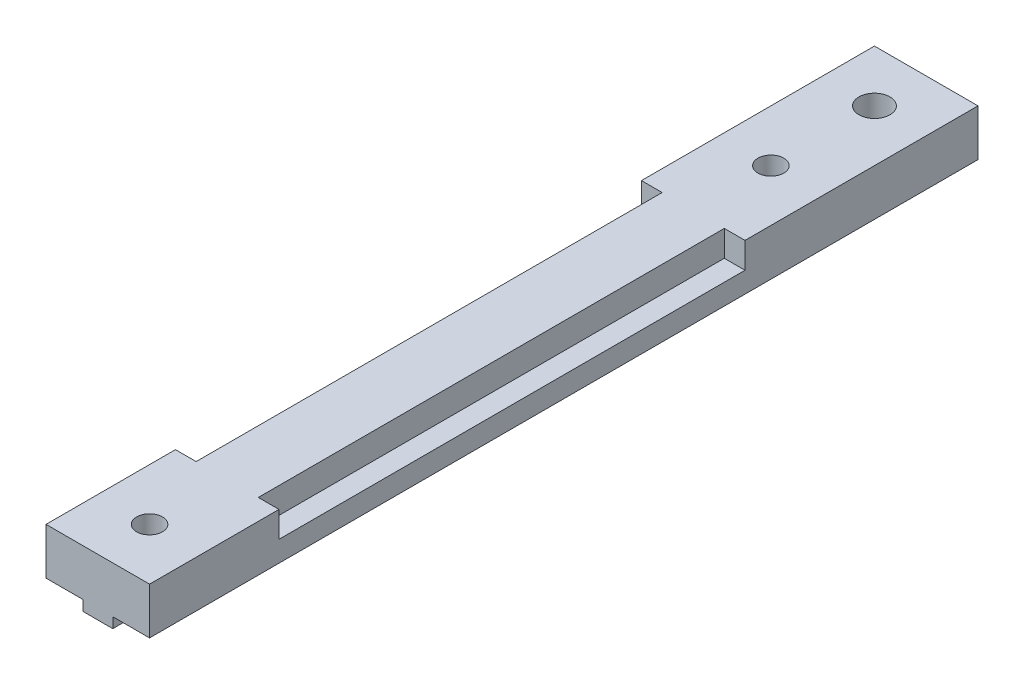
SolidWorks part; units mm, degrees
ref_plane "Front Plane" through (0, 0, 0) normal (0, 0, 1) x (1, 0, 0)
ref_plane "Top Plane" through (0, 0, 0) normal (0, 1, 0) x (1, 0, 0)
ref_plane "Right Plane" through (0, 0, 0) normal (1, 0, 0) x (0, 0, -1)
sketch "Sketch1" plane through (0, 0, 0) normal (0, 0, 1) x (1, 0, 0)
  line L0 (-5, 0) -> (5, 0)
  line L1 (5, 0) -> (5, -4.5)
  line L2 (5, -4.5) -> (1.45, -4.5)
  line L3 (1.45, -4.5) -> (1.45, -5.5)
  line L4 (1.45, -5.5) -> (-1.45, -5.5)
  line L5 (-1.45, -5.5) -> (-1.45, -4.5)
  line L6 (-1.45, -4.5) -> (-5, -4.5)
  line L7 (-5, -4.5) -> (-5, 0)
  point P6 (0, 0)
  point P9 (0, 0)
  dimension "D1" = 10
  dimension "D2" = 4.5
  dimension "D3" = 1
  dimension "D4" = 2.9
extrude "Main" add sketch "Sketch1" along normal blind 80
sketch "Sketch2" plane through (0, 0, 0) normal (0, 1, 0) x (1, 0, 0)
  line L0 (5, -80) -> (-5, -80) construction
  line L1 (5, 0) -> (-5, 0) construction
  circle A0 centre (0, -75) radius 1.25
  circle A1 centre (0, -15) radius 1.25
  circle A2 centre (0, -5) radius 1.5
  point P9 (0, 0)
  dimension "D1" = 2.5
  dimension "D4" = 3
  dimension "D2" = 5
  dimension "D3" = 60
  dimension "D5" = 5
extrude "Cut-Extrude1" cut sketch "Sketch2" against normal through all
sketch "Sketch3" plane through (0, 0, 0) normal (0, 1, 0) x (1, 0, 0)
  line L0 (-5, -80) -> (-5, 0) construction
  line L1 (-5, -22.5) -> (-3, -22.5)
  line L2 (-5, -22.5) -> (-5, -67.5)
  line L3 (-5, -67.5) -> (-3, -67.5)
  line L4 (-3, -22.5) -> (-3, -67.5)
  line L5 (5, -80) -> (5, 0) construction
  line L6 (3, -22.5) -> (5, -22.5)
  line L7 (3, -22.5) -> (3, -67.5)
  line L8 (3, -67.5) -> (5, -67.5)
  line L9 (5, -22.5) -> (5, -67.5)
  line L10 (5, -80) -> (-5, -80) construction
  dimension "D1" = 6
  dimension "D2" = 45
  dimension "D3" = 12.5
extrude "Cut-Extrude2" cut sketch "Sketch3" against normal blind 2.5
